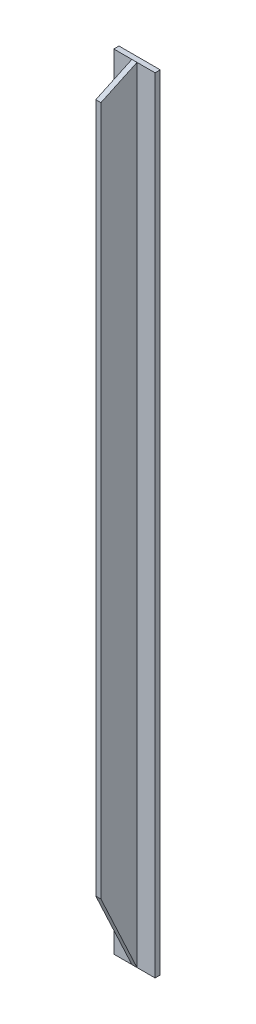
SolidWorks part; units mm, degrees
ref_plane "Front Plane" through (0, 0, 0) normal (0, 0, 1) x (1, 0, 0)
ref_plane "Top Plane" through (0, 0, 0) normal (0, 1, 0) x (1, 0, 0)
ref_plane "Right Plane" through (0, 0, 0) normal (1, 0, 0) x (0, 0, -1)
sketch "Sketch2" plane through (0, 0, 0) normal (0, 1, 0) x (1, 0, 0)
  line L1 (0, 0) -> (3.175, 0)
  line L2 (0, 0) -> (0, 22.225)
  line L4 (3.175, 0) -> (3.175, 22.225)
  line L7 (14.2875, 22.225) -> (3.175, 22.225)
  line L8 (14.2875, 22.225) -> (14.2875, 25.4)
  line L9 (14.2875, 25.4) -> (-11.1125, 25.4)
  line L10 (-11.1125, 22.225) -> (-11.1125, 25.4)
  line L14 (0, 22.225) -> (-11.1125, 22.225)
  point P0 (0, 0)
  point P3 (0, 0)
  dimension "D1" = 25.4
  dimension "D2" = 25.4
  dimension "D3" = 3.175
  dimension "D4" = 3.175
extrude "Boss-Extrude1" add sketch "Sketch2" along normal blind 482.6
sketch "Sketch4" plane through (3.175, 0, 0) normal (1, 0, 0) x (0, 0, -1)
  line L5 (22.225, 0) -> (0, 47.6617)
  line L6 (0, 482.6) -> (0, 0) construction
  line L7 (0, 47.6617) -> (0, 0)
  line L8 (0, 0) -> (22.225, 0)
  line L9 (22.225, 482.6) -> (0, 472.2363)
  line L10 (0, 472.2363) -> (0, 482.6)
  line L11 (0, 482.6) -> (22.225, 482.6)
  dimension "D1" = 25
  dimension "D2" = 65
extrude "Cut-Extrude1" cut sketch "Sketch4" against normal blind 438.15
